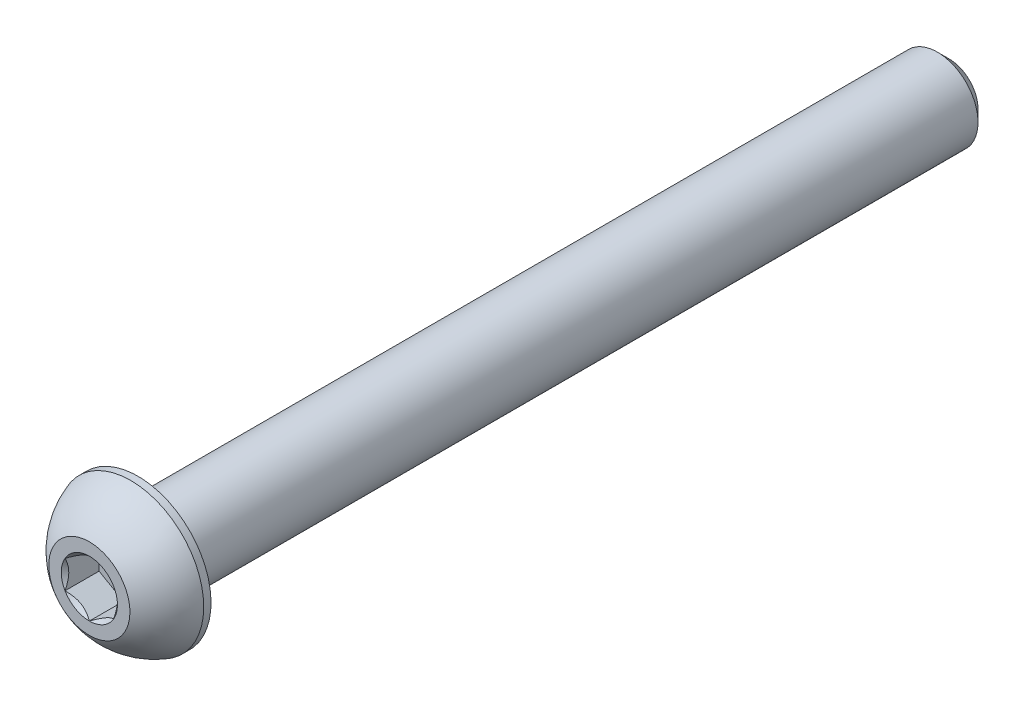
SolidWorks part; units mm, degrees
ref_plane "Front Plane" through (0, 0, 0) normal (0, 0, 1) x (1, 0, 0)
ref_plane "Top Plane" through (0, 0, 0) normal (0, 1, 0) x (1, 0, 0)
ref_plane "Right Plane" through (0, 0, 0) normal (1, 0, 0) x (0, 0, -1)
sketch "Sketch1" plane through (0, 0, 0) normal (1, 0, 0) x (0, 0, -1)
  line L0 (-13.25, 0) -> (13.25, 0) construction
  line L1 (-11.75, 2.25) -> (-11.75, -2.25) construction
  line L2 (13.25, 1.25) -> (13.25, -1.25) construction
  line L3 (13.2219, 1.2987) -> (13.4469, 0.909) construction
  line L4 (13.4469, 0.909) -> (13.6719, 1.2987) construction
  line L5 (13.6719, 1.2987) -> (13.2219, 1.2987) construction
  line L6 (13.25, 1.25) -> (13.6437, 1.25) construction
  line L7 (13.4469, 1.2987) -> (13.4469, 1.25) construction
  line L8 (13.4469, 1.25) -> (13.4469, 0.9577) construction
  line L9 (13.4469, 0.9577) -> (13.4469, 0.909) construction
  line L10 (13.4187, 0.9577) -> (13.475, 0.9577)
  line L11 (13.2359, 1.2744) -> (13.6578, 1.2744)
  line L12 (13.475, 0.9577) -> (13.6578, 1.2744)
  line L13 (13.4187, 0.9577) -> (13.2359, 1.2744)
  line L14 (-13.25, 0.75) -> (-13.25, -0.75) construction
  line L15 (13.25, 1.25) -> (-11.75, 1.25) construction
  point P3 (-11.75, 0)
  point P6 (-12.2, 0)
  point P21 (13.4469, 1.2744)
  point P24 (-11.975, 2.25)
  point P25 (12.125, -1.25)
  point P26 (-13.25, 1.25)
  dimension "Head Height" = 1.5
  dimension "Length" = 25
  dimension "Head Dia" = 4.5
  dimension "Thread Dia" = 2.5
  dimension "Pitch" = 0.45
  dimension "D2" = 0.0563
  dimension "Drive Size" = 1.5
  dimension "D1" = 1.05
  dimension "D3" = 0.225
  dimension "D4" = 1.125
sketch "Sketch2" plane through (0, 0, 0) normal (1, 0, 0) x (0, 0, -1)
  line L0 (-13.25, 0) -> (13.25, 0)
  line L1 (13.25, 0) -> (13.25, 0.89)
  line L2 (13.25, 1.25) -> (13.25, -1.25) construction
  line L3 (13.25, 0.89) -> (12.89, 1.25)
  line L4 (12.89, 1.25) -> (-11.75, 1.25)
  line L5 (-11.75, 2.25) -> (-11.75, -2.25) construction
  line L6 (-11.75, 1.25) -> (-11.75, 2.25)
  line L7 (-11.75, 2.25) -> (-11.975, 2.25)
  line L8 (13.25, 1.25) -> (13.6437, 1.25) construction
  line L9 (-13.25, 0) -> (-13.25, 1.25)
  arc A0 (-13.25, 1.25) -> (-11.975, 2.25) centre (-11.24, 0) cw
  dimension "D1" = 0.36
  dimension "D2" = 45
revolve "Revolve1" add sketch "Sketch2" angle 360 about L0
sketch "Sketch3" plane through (0, 0, 13.25) normal (0, 0, 1) x (1, 0, 0)
  line L1 (0, 0.866) -> (-0.75, 0.433)
  line L2 (-0.75, 0.433) -> (-0.75, -0.433)
  line L3 (-0.75, -0.433) -> (0, -0.866)
  line L4 (0, -0.866) -> (0.75, -0.433)
  line L5 (0.75, -0.433) -> (0.75, 0.433)
  line L6 (0.75, 0.433) -> (0, 0.866)
  circle A0 centre (0, 0) radius 0.75 construction
  dimension "D1" = 1.5
extrude "Cut-Extrude1" cut sketch "Sketch3" against normal up to vertex (1.05 mm away) up to point (0, 0, 12.2)
sketch "Sketch4" plane through (0, 0, 13.25) normal (0, 0, 1) x (1, 0, 0)
  circle A0 centre (0, 0) radius 0.866
extrude "Cut-Extrude2" cut sketch "Sketch4" against normal blind 10 draft 45
split "Split1" [suppressed] bodies to split 106
sketch "Sketch5" [suppressed] plane through (0, 0, -13.25) normal (0, 0, -1) x (-1, 0, 0)
  circle A0 centre (0, 0) radius 1.25 construction
  circle A1 centre (0, 0) radius 1.25
curve "Helix/Spiral1" [suppressed] pitch 0.45 height 25.45 turns 56.5556
sketch "Sketch6" [suppressed] plane through (0, 0, 0) normal (1, 0, 0) x (0, 0, -1)
  line L0 (13.4187, 0.9577) -> (13.475, 0.9577) construction
  line L1 (13.4187, 0.9577) -> (13.2359, 1.2744) construction
  line L2 (13.2359, 1.2744) -> (13.6578, 1.2744) construction
  line L3 (13.475, 0.9577) -> (13.6578, 1.2744) construction
  line L4 (13.4187, 0.9577) -> (13.475, 0.9577)
  line L5 (13.4187, 0.9577) -> (13.2359, 1.2744)
  line L6 (13.2359, 1.2744) -> (13.6578, 1.2744)
  line L7 (13.475, 0.9577) -> (13.6578, 1.2744)
sweep "Cut-Sweep1" [suppressed] cut profiles "Sketch6" path "Helix/Spiral1"
sketch "Sketch7" [suppressed] plane through (0, 0, 11.75) normal (0, 0, -1) x (-1, 0, 0)
  circle A1 centre (0, 0) radius 1.25
  circle A2 centre (0, 0) radius 1.25
  dimension "D1" = 0
extrude "Boss-Extrude1" [suppressed] add sketch "Sketch7" along normal blind 10 draft 30
equation "\"D2@Sketch1\" = \"Pitch@Sketch1\" / 8"
equation "\"D1@Sketch1\"=\"Drive Size@Sketch1\"*.7"
equation "\"D3@Sketch1\"=\"Head Height@Sketch1\"*.15"
equation "\"D1@Sketch2\"=\"Pitch@Sketch1\"*.8"
equation "\"D1@Sketch3\"=\"Drive Size@Sketch1\""
equation "\"D4@Helix/Spiral1\"=\"Pitch@Sketch1\""
equation "\"D3@Helix/Spiral1\"=\"Length@Sketch1\"+\"Pitch@Sketch1\""
equation "\"D4@Sketch1\"=\"Pitch@Sketch1\"*2.5"
